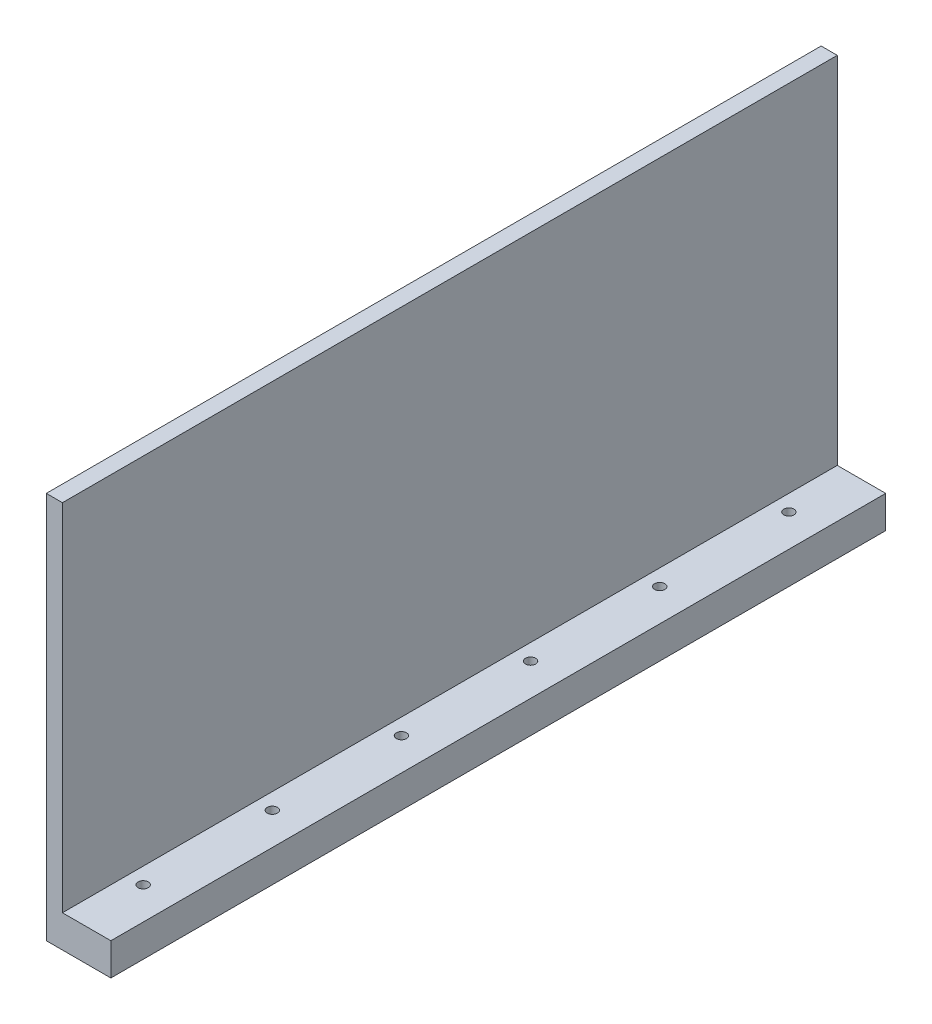
SolidWorks part; units mm, degrees
ref_plane "Front Plane" through (0, 0, 0) normal (0, 0, 1) x (1, 0, 0)
ref_plane "Top Plane" through (0, 0, 0) normal (0, 1, 0) x (1, 0, 0)
ref_plane "Right Plane" through (0, 0, 0) normal (1, 0, 0) x (0, 0, -1)
sketch "Sketch1" plane through (0, 0, 0) normal (0, 1, 0) x (1, 0, 0)
  line L1 (-6.35, -76.2) -> (6.35, -76.2)
  line L2 (-6.35, -76.2) -> (-6.35, 76.2)
  line L3 (-6.35, 76.2) -> (6.35, 76.2)
  line L4 (6.35, -76.2) -> (6.35, 76.2)
  line L5 (-6.35, -76.2) -> (6.35, 76.2) construction
  line L6 (-6.35, 76.2) -> (6.35, -76.2) construction
  point P0 (0, 0)
  dimension "D1" = 152.4
  dimension "D2" = 12.7
extrude "Boss-Extrude1" add sketch "Sketch1" along normal blind 76.2
sketch "Sketch2" plane through (0, 76.2, 0) normal (0, 1, 0) x (1, 0, 0)
  line L0 (-6.35, -76.2) -> (6.35, -76.2) construction
  line L1 (6.35, 76.2) -> (-3.175, 76.2)
  line L2 (6.35, 76.2) -> (6.35, -76.2)
  line L3 (6.35, -76.2) -> (-3.175, -76.2)
  line L4 (-3.175, 76.2) -> (-3.175, -76.2)
  line L5 (-6.35, 76.2) -> (-6.35, -76.2) construction
  dimension "D1" = 3.175
extrude "Cut-Extrude1" cut sketch "Sketch2" against normal offset from surface (69.85 mm away) 6.35 up to face at (0, 0, 0)
sketch "Sketch3" plane through (0, 6.35, 0) normal (0, 1, 0) x (1, 0, 0)
  line L0 (6.35, 76.2) -> (-3.175, 76.2) construction
  line L1 (6.35, 76.2) -> (-6.35, 76.2) construction
  circle A0 centre (0, 63.5) radius 1
  circle A5 centre (0, 38.1) radius 1
  circle A6 centre (0, 12.7) radius 1
  circle A7 centre (0, -12.7) radius 1
  circle A8 centre (0, -38.1) radius 1
  circle A9 centre (0, -63.5) radius 1
  point P15 (0, 76.2)
  dimension "D1" = 2
  dimension "D2" = 12.7
  dimension "D3" = 6
extrude "Cut-Extrude2" cut sketch "Sketch3" against normal through all
equation "\"D1@Sketch3\"=2mm"
